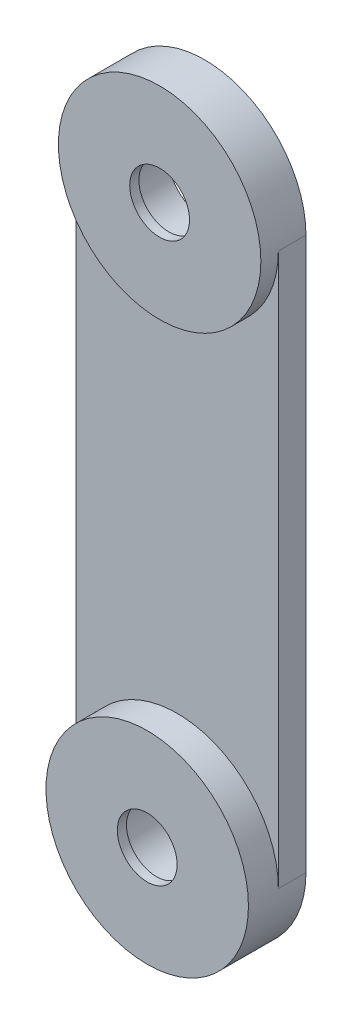
SolidWorks part; units mm, degrees
ref_plane "Plano frontal" through (0, 0, 0) normal (0, 0, 1) x (1, 0, 0)
ref_plane "Plano superior" through (0, 0, 0) normal (0, 1, 0) x (1, 0, 0)
ref_plane "Plano direito" through (0, 0, 0) normal (1, 0, 0) x (0, 0, -1)
other "Centro da massa"
sketch "Esboço1" plane through (0, 0, 0) normal (0, 0, 1) x (1, 0, 0)
  circle A3 centre (13.3842, -8.4275) radius 11 construction
  circle A5 centre (13.3842, -8.4275) radius 11
extrude "Ressalto-extrusão1" add sketch "Esboço1" against normal offset from surface (1.9 mm away) 2 offset beyond the face yes
sketch "Esboço3" plane through (0, 0, -1.9) normal (0, 0, -1) x (-1, 0, 0)
  line L0 (-24.3842, -8.4275) -> (-24.3842, -68.4275)
  line L1 (-2.3842, -8.4275) -> (-2.3842, -68.4275)
  arc A0 (-24.3842, -68.4275) -> (-2.3842, -68.4275) centre (-13.3842, -68.4275) ccw
  arc A7 (-2.3842, -8.4275) -> (-24.3842, -8.4275) centre (-13.3842, -8.4275) ccw
  circle A8 centre (-13.3842, -8.4275) radius 11 construction
  dimension "D1" = 60
extrude "Ressalto-extrusão3" add sketch "Esboço3" along normal blind 3
sketch "Esboço4" plane through (0, 0, -4.9) normal (0, 0, -1) x (-1, 0, 0)
  circle A0 centre (-13.3842, -8.4275) radius 3.25 construction
  circle A1 centre (-13.3842, -8.4275) radius 3.25
extrude "Corte-extrusão2" cut sketch "Esboço4" against normal through all
sketch "Esboço5" plane through (0, 0, -4.9) normal (0, 0, -1) x (-1, 0, 0)
  circle A0 centre (-13.3842, -8.4275) radius 4 construction
  circle A1 centre (-13.3842, -8.4275) radius 4
extrude "Corte-extrusão5" cut sketch "Esboço5" against normal offset from surface (3.9 mm away) 1 up to face at (10.1342, -8.4275, 0)
sketch "Esboço6" plane through (0, 0, -1.9) normal (0, 0, 1) x (1, 0, 0)
  circle A0 centre (13.3842, -68.4275) radius 11
  arc A1 (2.3842, -68.4275) -> (24.3842, -68.4275) centre (13.3842, -68.4275) ccw construction
extrude "Ressalto-extrusão4" add sketch "Esboço6" along normal offset from surface (3.25 mm away) 1 offset beyond the face yes
sketch "Esboço7" plane through (0, 0, -4.9) normal (0, 0, -1) x (-1, 0, 0)
  circle A0 centre (-13.3842, -68.4275) radius 4 construction
  circle A1 centre (-13.3842, -68.4275) radius 4
extrude "Corte-extrusão6" cut sketch "Esboço7" against normal offset from surface (5.25 mm away) 1 up to face at (13.3842, -79.4275, 1.35)
sketch "Esboço8" plane through (0, 0, -4.9) normal (0, 0, -1) x (-1, 0, 0)
  circle A0 centre (-13.3842, -68.4275) radius 3.25 construction
  circle A1 centre (-13.3842, -68.4275) radius 3.25
extrude "Corte-extrusão7" cut sketch "Esboço8" against normal through all
